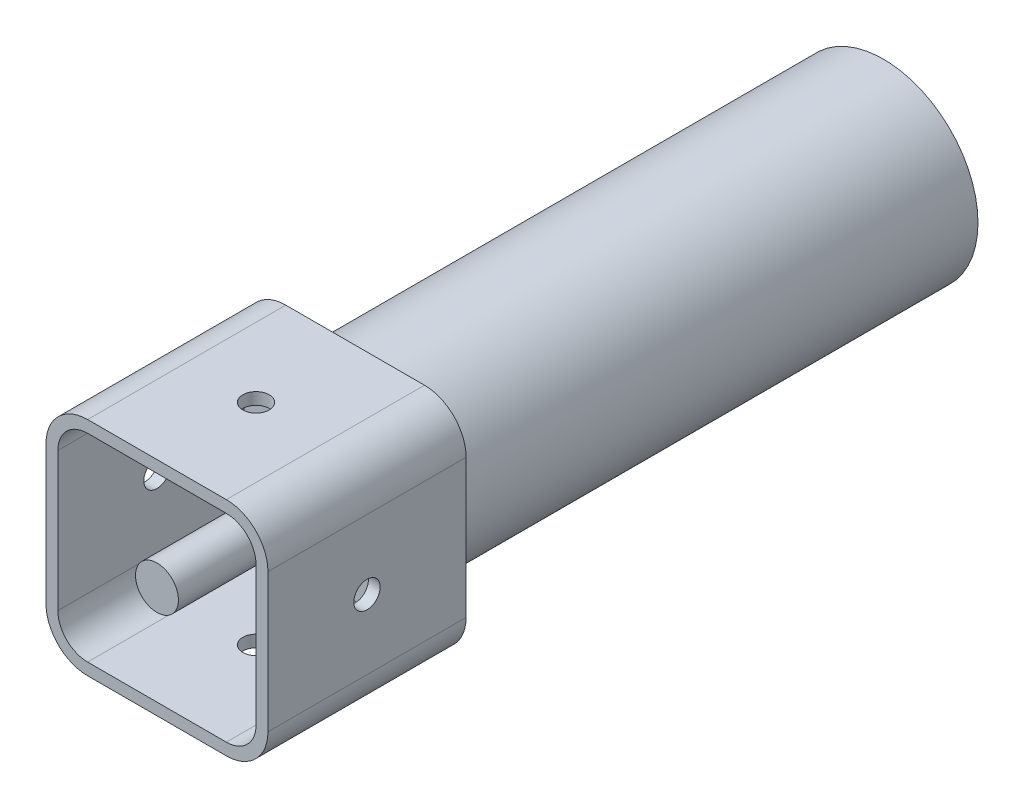
SolidWorks part; units mm, degrees
ref_plane "前基準面" through (0, 0, 0) normal (0, 0, 1) x (1, 0, 0)
ref_plane "上基準面" through (0, 0, 0) normal (0, 1, 0) x (1, 0, 0)
ref_plane "右基準面" through (0, 0, 0) normal (1, 0, 0) x (0, 0, -1)
sketch "草圖1" plane through (0, 0, 0) normal (0, 0, 1) x (1, 0, 0)
  line L0 (0, 0) -> (0, 25.038) construction
  line L1 (10.5, 15) -> (-10.5, 15) construction
  line L2 (15, 10.5) -> (15, -10.5) construction
  line L3 (10.5, -15) -> (-10.5, -15) construction
  line L4 (-15, 10.5) -> (-15, -10.5) construction
  line L5 (15, 15) -> (-15, -15) construction
  line L6 (15, -15) -> (-15, 15) construction
  line L7 (0, 0) -> (-30.1651, 0) construction
  line L8 (10.5, 16.8) -> (-10.5, 16.8)
  line L9 (-16.8, 10.5) -> (-16.8, -10.5)
  line L10 (10.5, -16.8) -> (-10.5, -16.8)
  line L11 (16.8, 10.5) -> (16.8, -10.5)
  line L12 (15, 15) -> (-15, 15) construction
  line L13 (15, 15) -> (15, -15) construction
  line L14 (15, -15) -> (-15, -15) construction
  line L15 (-15, 15) -> (-15, -15) construction
  line L16 (16.8, 16.8) -> (-16.8, 16.8) construction
  line L17 (16.8, 16.8) -> (16.8, -16.8) construction
  line L18 (16.8, -16.8) -> (-16.8, -16.8) construction
  line L19 (-16.8, 16.8) -> (-16.8, -16.8) construction
  circle A0 centre (0, 0) radius 3.25
  arc A1 (10.5, 15) -> (15, 10.5) centre (10.5, 10.5) cw construction
  arc A2 (15, -10.5) -> (10.5, -15) centre (10.5, -10.5) cw construction
  arc A3 (-10.5, -15) -> (-15, -10.5) centre (-10.5, -10.5) cw construction
  arc A4 (-15, 10.5) -> (-10.5, 15) centre (-10.5, 10.5) cw construction
  arc A5 (10.5, 16.8) -> (16.8, 10.5) centre (10.5, 10.5) cw
  arc A6 (10.5, -16.8) -> (16.8, -10.5) centre (10.5, -10.5) ccw
  arc A7 (-16.8, -10.5) -> (-10.5, -16.8) centre (-10.5, -10.5) ccw
  arc A8 (-10.5, 16.8) -> (-16.8, 10.5) centre (-10.5, 10.5) ccw
  point P0 (0, 0)
  dimension "D4" = 6.5
  dimension "D5" = 4.5
  dimension "D6" = 6.3
  dimension "D1" = 30
  dimension "D2" = 30
  dimension "D3" = 1.8
extrude "填料-伸長1" add sketch "草圖1" along normal blind 30 contours A0 | L8 A8 L9 A7 L10 A6 L11 A5 A0 region at (14.6188, 14.6188, 0) region at (0, 0, 0)
shell "薄殼1" thickness 1.8 removed face at (0, 0, 30)
extrude "填料-伸長2" add sketch "草圖1<3>" along normal blind 30 contours A0 region at (0, 0, 0)
sketch "草圖1<3>" plane through (0, 0, 0) normal (0, 0, 1) x (1, 0, 0) same geometry as "草圖1"
sketch "草圖2" plane through (0, 16.8, 0) normal (0, 1, 0) x (1, 0, 0)
  line L0 (0, 0) -> (0, -15) construction
  line L1 (0, -15) -> (16.8, -15) construction
  line L2 (16.8, -30) -> (16.8, 0) construction
  circle A0 centre (0, -15) radius 2
  dimension "D1" = 4
extrude "除料-伸長1" cut sketch "草圖2" against normal up to next
pattern_circular "環狀複製排列1" count 4 over 360 about axis through (0, 0, 30) along (0, 0, -1) of "除料-伸長1"
sketch "草圖3" plane through (0, 0, 0) normal (0, 0, -1) x (-1, 0, 0)
  circle A0 centre (0, 0) radius 12.5
  circle A1 centre (0, 0) radius 14.3
  dimension "D1" = 25
  dimension "D2" = 1.8
extrude "填料-伸長3" add sketch "草圖3" along normal blind 80
sketch "草圖4" plane through (0, 0, 0) normal (0, 1, 0) x (1, 0, 0)
  line L0 (0, 50) -> (0, 0) construction
  line L1 (-2.5, 82.6656) -> (2.5, 82.6656)
  line L2 (-2.5, 82.6656) -> (-2.5, 50)
  line L3 (-2.5, 50) -> (2.5, 50) construction
  line L4 (2.5, 82.6656) -> (2.5, 50)
  line L5 (14.3, 80) -> (-14.3, 80) construction
  arc A0 (2.5, 50) -> (-2.5, 50) centre (0, 50) cw
  dimension "D1" = 5
  dimension "D2" = 30
extrude "除料-伸長2" cut sketch "草圖4" against normal up to next
fillet "圓角1" radius 2 1 edges at (14.3, 0, 0)
